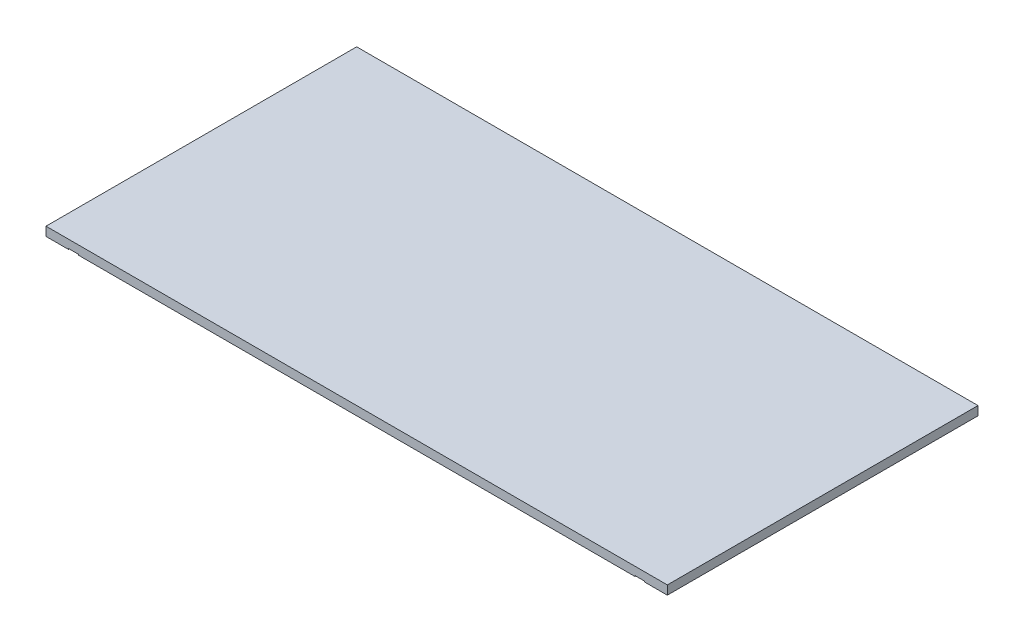
SolidWorks part; units mm, degrees
material "Cedar"
ref_plane "Front Plane" through (0, 0, 0) normal (0, 0, 1) x (1, 0, 0)
ref_plane "Top Plane" through (0, 0, 0) normal (0, 1, 0) x (1, 0, 0)
ref_plane "Right Plane" through (0, 0, 0) normal (1, 0, 0) x (0, 0, -1)
sketch "Sketch1" plane through (0, 0, 0) normal (0, 1, 0) x (1, 0, 0)
  line L1 (-609.6, -304.8) -> (609.6, -304.8)
  line L2 (-609.6, -304.8) -> (-609.6, 304.8)
  line L3 (-609.6, 304.8) -> (609.6, 304.8)
  line L4 (609.6, -304.8) -> (609.6, 304.8)
  line L5 (-609.6, -304.8) -> (609.6, 304.8) construction
  line L6 (-609.6, 304.8) -> (609.6, -304.8) construction
  point P0 (0, 0)
  dimension "D1" = 1219.2
  dimension "D2" = 609.6
extrude "Boss-Extrude1" add sketch "Sketch1" along normal blind 17.4752
sketch "Sketch2" plane through (0, 0, 0) normal (0, 1, 0) x (1, 0, 0)
  line L0 (609.6, 304.8) -> (-609.6, 304.8) construction
  line L1 (-565.15, 304.8) -> (-546.1, 304.8)
  line L2 (-565.15, 304.8) -> (-565.15, -304.8)
  line L3 (-565.15, -304.8) -> (-546.1, -304.8)
  line L4 (-546.1, 304.8) -> (-546.1, 9.525)
  line L5 (-609.6, -304.8) -> (609.6, -304.8) construction
  line L7 (-546.1, 9.525) -> (101.6, 9.525)
  line L8 (-546.1, 9.525) -> (-546.1, -9.525) construction
  line L9 (-546.1, -9.525) -> (-120.65, -9.525)
  line L12 (565.15, 304.8) -> (546.1, 304.8)
  line L13 (565.15, 304.8) -> (565.15, -304.8)
  line L14 (565.15, -304.8) -> (546.1, -304.8)
  line L15 (546.1, 304.8) -> (546.1, 9.525)
  line L17 (-120.65, -9.525) -> (-101.6, -9.525)
  line L18 (-120.65, -9.525) -> (-120.65, -304.8) construction
  line L19 (-120.65, -304.8) -> (-101.6, -304.8) construction
  line L20 (-101.6, -9.525) -> (-101.6, -304.8) construction
  line L21 (-546.1, -9.525) -> (-546.1, -304.8)
  line L23 (101.6, -9.525) -> (101.6, -304.8) construction
  line L24 (101.6, -304.8) -> (120.65, -304.8) construction
  line L25 (120.65, -9.525) -> (120.65, -304.8) construction
  line L26 (-101.6, -9.525) -> (101.6, -9.525)
  line L27 (0, 0) -> (0, -9.525) construction
  line L28 (546.1, -9.525) -> (546.1, -304.8)
  line L29 (120.65, -9.525) -> (546.1, -9.525)
  line L30 (-565.15, 304.8) -> (-609.6, 304.8) construction
  line L31 (565.15, 304.8) -> (609.6, 304.8) construction
  line L32 (-609.6, 304.8) -> (-609.6, -304.8) construction
  line L33 (120.65, 9.525) -> (546.1, 9.525)
  line L35 (101.6, 9.525) -> (101.6, 304.8)
  line L36 (101.6, 304.8) -> (120.65, 304.8)
  line L37 (120.65, 9.525) -> (120.65, 304.8)
  line L38 (-546.1, 0) -> (-609.6, 0) construction
  line L39 (101.6, -9.525) -> (120.65, -9.525)
  dimension "D1" = 19.05
  dimension "D3" = 425.45
  dimension "D4" = 203.2
  dimension "D5" = 44.45
extrude "Cut-Extrude1" cut sketch "Sketch2" along normal blind 1.5875
sketch "Sketch5" plane through (0, 1.5875, 0) normal (0, -1, 0) x (-1, 0, 0)
  line L0 (-546.1, -9.525) -> (546.1, -9.525) construction
  point P0 (0, -9.525)
sketch "Sketch6" plane through (0, 17.4752, 0) normal (0, 1, 0) x (1, 0, 0)
  line L0 (-609.6, -304.8) -> (609.6, -304.8) construction
  line L2 (-609.6, 304.8) -> (-609.6, -304.8)
  line L3 (-609.6, -304.8) -> (-590.55, -304.8)
  line L4 (-590.55, 285.75) -> (-590.55, -304.8)
  line L5 (546.1, -304.8) -> (565.15, -304.8) construction
  line L8 (-590.55, 285.75) -> (590.55, 285.75)
  line L11 (609.6, 304.8) -> (609.6, -304.8)
  line L12 (609.6, -304.8) -> (590.55, -304.8)
  line L13 (590.55, 285.75) -> (590.55, -304.8)
  line L14 (609.6, 304.8) -> (-609.6, 304.8) construction
  line L15 (609.6, 304.8) -> (-609.6, 304.8)
  line L16 (-590.55, 285.75) -> (-590.55, 304.8) construction
  line L17 (0, 0) -> (0, 285.75)
  line L18 (0, 0) -> (0, -304.8)
